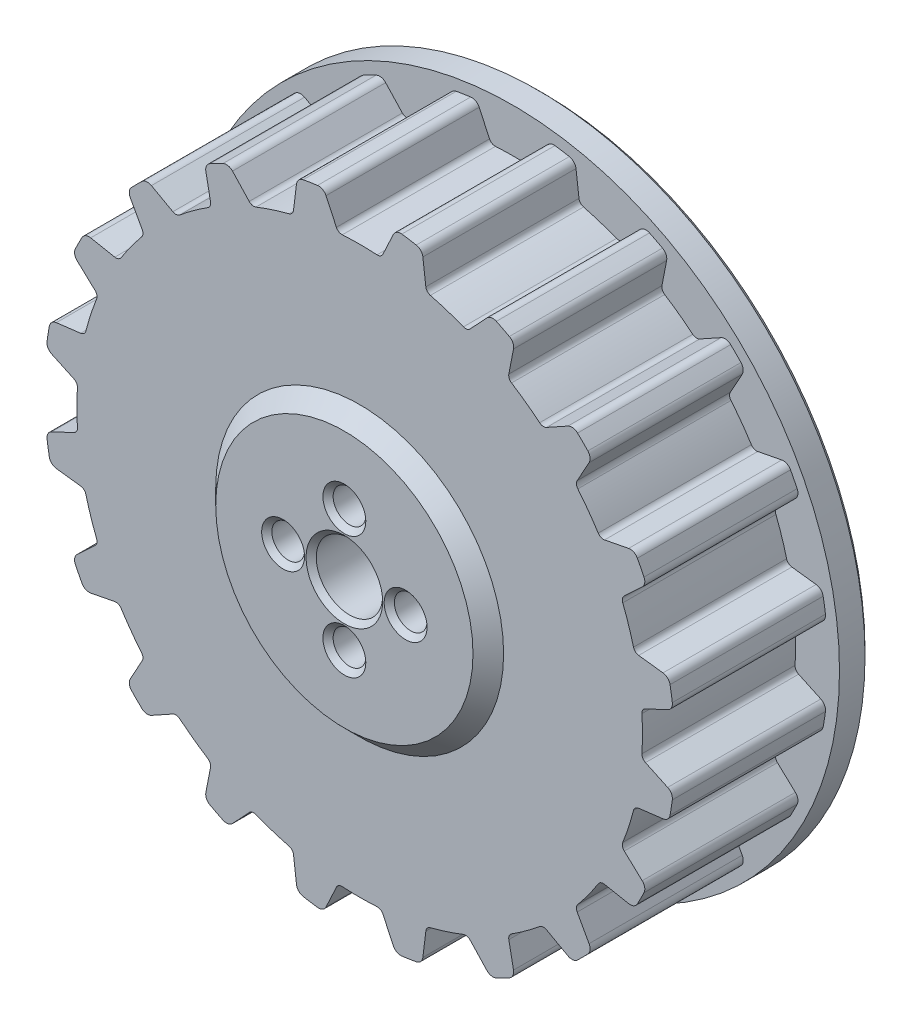
SolidWorks part; units mm, degrees
material "ABS"
ref_plane "正面" through (0, 0, 0) normal (0, 0, 1) x (1, 0, 0)
ref_plane "平面" through (0, 0, 0) normal (0, 1, 0) x (1, 0, 0)
ref_plane "右側面" through (0, 0, 0) normal (1, 0, 0) x (0, 0, -1)
sketch "ｽｹｯﾁ1" plane through (0, 0, 0) normal (0, 0, 1) x (1, 0, 0)
  line L0 (0, 2.608) -> (0, -1.4358) construction
  line L1 (-2.2806, 27.9931) -> (-3.295, 30.1684)
  line L2 (2.2806, 27.9931) -> (3.295, 30.1684)
  line L3 (-4.8338, 30.5196) -> (0, 0) construction
  line L4 (0, 0) -> (4.8338, 30.5196) construction
  line L5 (-4.8338, 30.5196) -> (-0.7822, 4.9384)
  line L6 (0.7822, 4.9384) -> (4.8338, 30.5196)
  arc A0 (1.7, 27.6478) -> (-1.7, 27.6478) centre (0, 0) ccw
  arc A1 (-1.7, 27.6478) -> (-2.2806, 27.9931) centre (-1.7368, 28.2467) cw
  arc A2 (-3.295, 30.1684) -> (-4.1269, 30.6232) centre (-4.02, 29.8303) ccw
  arc A3 (-4.1269, 30.6232) -> (-4.8338, 30.5196) centre (0, 0) ccw
  arc A4 (4.1269, 30.6232) -> (4.8338, 30.5196) centre (0, 0) cw
  arc A5 (3.295, 30.1684) -> (4.1269, 30.6232) centre (4.02, 29.8303) cw
  arc A6 (1.7, 27.6478) -> (2.2806, 27.9931) centre (1.7368, 28.2467) ccw
  arc A7 (-0.7822, 4.9384) -> (0.7822, 4.9384) centre (0, 0) ccw
  dimension "D1" = 3.2
  dimension "D2" = 0.6
  dimension "D3" = 0.8
  dimension "D4" = 30.9
  dimension "D8" = 5
  dimension "D5" = 25
  dimension "D6" = 3.4
  dimension "D7" = 18
extrude "ﾎﾞｽ - 押し出し1" add sketch "ｽｹｯﾁ1" along normal blind 17
pattern_circular "円形ﾊﾟﾀｰﾝ1" count 20 over 360 about axis through (0, 0, 17) along (0, 0, -1) of "ﾎﾞｽ - 押し出し1" reverse direction yes
sketch "ｽｹｯﾁ4" plane through (0, 0, 0) normal (0, 0, -1) x (-1, 0, 0)
  circle A0 centre (0, 0) radius 32
  dimension "D1" = 64
extrude "ﾎﾞｽ - 押し出し3" add sketch "ｽｹｯﾁ4" along normal blind 1
sketch "ｽｹｯﾁ5" plane through (0, 0, 0) normal (0, 0, 1) x (1, 0, 0)
  circle A0 centre (0, 0) radius 32
  circle A1 centre (0, 0) radius 32 construction
extrude "ﾎﾞｽ - 押し出し4" add sketch "ｽｹｯﾁ5" along normal blind 2
sketch "ｽｹｯﾁ2" plane through (0, 0, 17) normal (0, 0, 1) x (1, 0, 0)
  line L0 (0, 0) -> (0, 6) construction
  line L1 (0, 0) -> (6, 0) construction
  line L2 (0, 0) -> (0, -6) construction
  line L3 (0, 0) -> (-6, 0) construction
  circle A0 centre (0, 0) radius 3.25
  circle A1 centre (0, 6) radius 1.6
  circle A2 centre (6, 0) radius 1.6
  circle A3 centre (0, -6) radius 1.6
  circle A4 centre (-6, 0) radius 1.6
  point P17 (0, 0)
  dimension "D1" = 6.5
  dimension "D3" = 3.2
  dimension "D2" = 6
  dimension "D4" = 4
extrude "ｶｯﾄ - 押し出し2" cut sketch "ｽｹｯﾁ2" against normal through all
sketch "ｽｹｯﾁ6" plane through (0, 0, 17) normal (0, 0, 1) x (1, 0, 0)
  circle A0 centre (0, 0) radius 12.5
  circle A1 centre (0, -6) radius 1.6 construction
  circle A2 centre (6, 0) radius 1.6 construction
  circle A3 centre (-6, 0) radius 1.6 construction
  circle A4 centre (0, 0) radius 3.25 construction
  circle A5 centre (0, 6) radius 1.6 construction
  circle A6 centre (0, -6) radius 1.6
  circle A7 centre (6, 0) radius 1.6
  circle A8 centre (-6, 0) radius 1.6
  circle A9 centre (0, 0) radius 3.25
  circle A10 centre (0, 6) radius 1.6
  dimension "D1" = 25
extrude "ﾎﾞｽ - 押し出し5" add sketch "ｽｹｯﾁ6" along normal blind 1.5
chamfer "面取り1" distance 0.5 angle 45 5 edges at (7.6, 0, 18.5) (1.6, -6, 18.5) (3.25, 0, 18.5) (-4.4, 0, 18.5) (1.6, 6, 18.5)
chamfer "面取り2" distance 1.6 angle 45 1 edges at (12.5, 0, 17)
chamfer "面取り3" distance 0.5 angle 45 6 edges at (-32, 0, -1) (3.25, 0, -1) (-4.4, 0, -1) (1.6, -6, -1) (7.6, 0, -1) (1.6, 6, -1)
